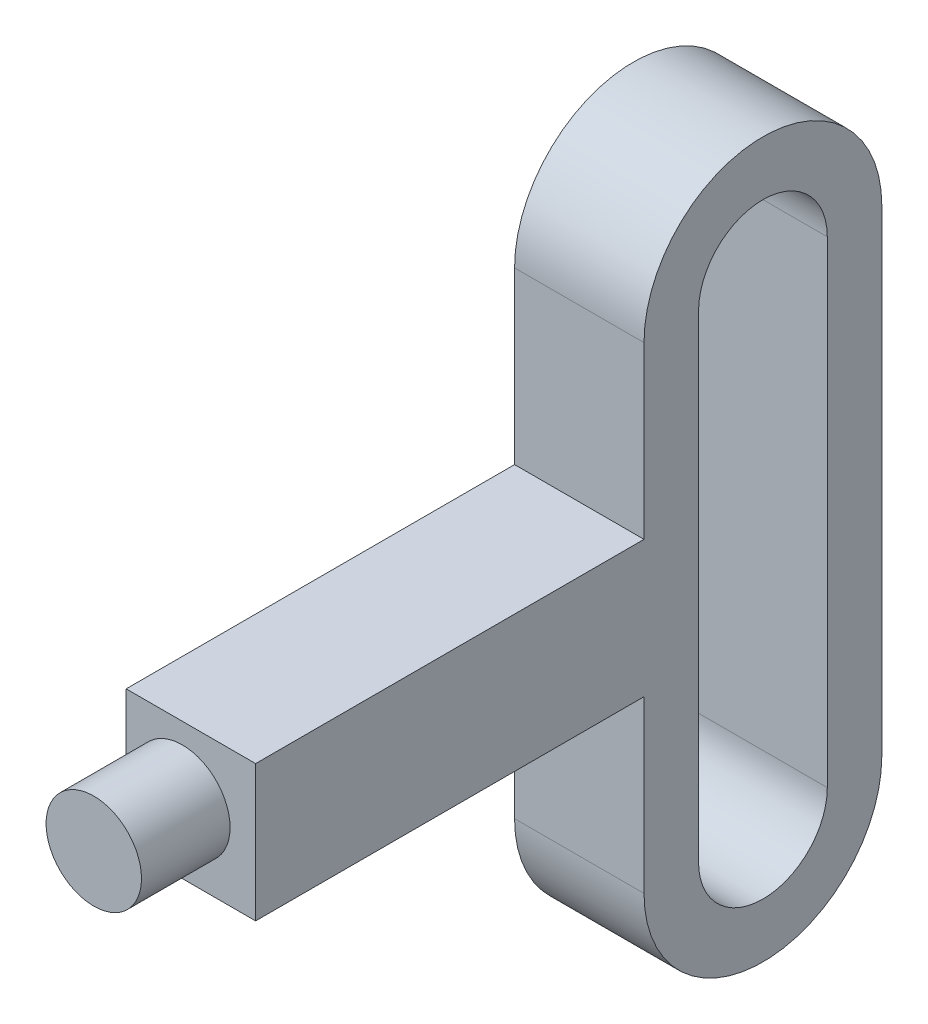
SolidWorks part; units mm, degrees
ref_plane "Front Plane" through (0, 0, 0) normal (0, 0, 1) x (1, 0, 0)
ref_plane "Top Plane" through (0, 0, 0) normal (0, 1, 0) x (1, 0, 0)
ref_plane "Right Plane" through (0, 0, 0) normal (1, 0, 0) x (0, 0, -1)
sketch "Sketch2" plane through (0, 0, 0) normal (1, 0, 0) x (0, 0, -1)
  line L0 (-22.16, -44.45) -> (-22.16, 44.45)
  line L1 (0, -44.45) -> (0, 44.45) construction
  line L2 (-12, -44.45) -> (-12, 44.45)
  line L3 (12, -44.45) -> (12, 44.45)
  line L4 (22.16, -44.45) -> (22.16, 44.45)
  line L5 (0, 0) -> (-80.0365, 0) construction
  line L6 (-22.16, -12.7) -> (-111.06, -12.7)
  line L7 (-22.16, 0) -> (-111.06, 0) construction
  line L8 (-22.16, 0) -> (-22.16, 12.7)
  line L9 (-22.16, 12.7) -> (-111.06, 12.7)
  line L10 (-111.06, -12.7) -> (-111.06, 12.7)
  arc A0 (-12, -44.45) -> (12, -44.45) centre (0, -44.45) ccw
  arc A1 (12, 44.45) -> (-12, 44.45) centre (0, 44.45) ccw
  arc A2 (22.16, 44.45) -> (-22.16, 44.45) centre (0, 44.45) ccw
  arc A3 (-22.16, -44.45) -> (22.16, -44.45) centre (0, -44.45) ccw
  point P5 (0, 0)
  point P16 (-40.0182, 0)
  dimension "D2" = 12
  dimension "D1" = 88.9
  dimension "D4" = 88.9
  dimension "D5" = 25.4
  dimension "D3" = 10.16
extrude "Boss-Extrude2" add sketch "Sketch2" along normal blind 24.13 contours L10 L6 L0 L9 | L0 A3 L4 A2 A1 L3 A0 L2 region at (0, -28.575, 20.756) region at (0, 0, 66.61)
sketch "Sketch3" plane through (0, 0, 111.06) normal (0, 0, 1) x (1, 0, 0)
  line L0 (0, 0) -> (24.13, 0) construction
  line L1 (0, -12.7) -> (0, 12.7) construction
  line L2 (24.13, -12.7) -> (24.13, 12.7) construction
  line L7 (0, 12.7) -> (0, -12.7)
  line L8 (0, -12.7) -> (24.13, -12.7)
  line L9 (24.13, -12.7) -> (24.13, 12.7)
  line L10 (24.13, 12.7) -> (0, 12.7)
  line L11 (0, 12.7) -> (0, -12.7)
  line L12 (0, -12.7) -> (24.13, -12.7)
  line L13 (24.13, -12.7) -> (24.13, 12.7)
  line L14 (24.13, 12.7) -> (0, 12.7)
  circle A1 centre (10.4775, 0) radius 13.6525 construction
  circle A2 centre (10.4775, 0) radius 8.89
  dimension "D1" = 27.305
  dimension "D3" = 17.78
  dimension "D2" = 0
extrude "Cut-Extrude3" cut sketch "Sketch3" against normal blind 16.51
